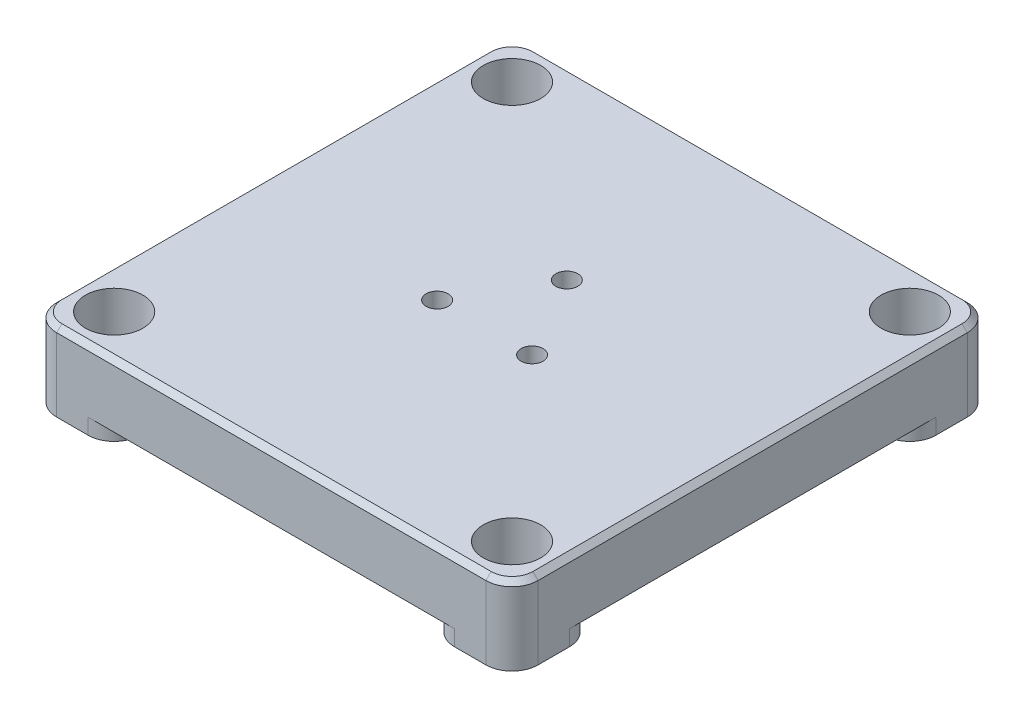
SolidWorks part; units mm, degrees
ref_plane "Спереди" through (0, 0, 0) normal (0, 0, 1) x (1, 0, 0)
ref_plane "Сверху" through (0, 0, 0) normal (0, 1, 0) x (1, 0, 0)
ref_plane "Справа" through (0, 0, 0) normal (1, 0, 0) x (0, 0, -1)
sketch "Эскиз1" plane through (0, 0, 0) normal (0, 1, 0) x (1, 0, 0)
  line L1 (-46.1, 46.1) -> (46.1, 46.1)
  line L2 (-46.1, 46.1) -> (-46.1, -46.1)
  line L3 (-46.1, -46.1) -> (46.1, -46.1)
  line L4 (46.1, 46.1) -> (46.1, -46.1)
  line L5 (-46.1, 46.1) -> (46.1, -46.1) construction
  line L6 (-46.1, -46.1) -> (46.1, 46.1) construction
  line L7 (38.1, 38.1) -> (-38.1, 38.1) construction
  line L8 (38.1, 38.1) -> (38.1, -38.1) construction
  line L9 (38.1, -38.1) -> (-38.1, -38.1) construction
  line L10 (-38.1, 38.1) -> (-38.1, -38.1) construction
  line L11 (38.1, 38.1) -> (-38.1, -38.1) construction
  line L12 (38.1, -38.1) -> (-38.1, 38.1) construction
  circle A0 centre (0, 0) radius 10.5 construction
  circle A1 centre (0, 10.5) radius 2.1
  circle A2 centre (-38.1, 38.1) radius 3.35
  circle A3 centre (38.1, 38.1) radius 3.35
  circle A4 centre (38.1, -38.1) radius 3.35
  circle A5 centre (-38.1, -38.1) radius 3.35
  circle A6 centre (9.0933, -5.25) radius 2.1
  circle A7 centre (-9.0933, -5.25) radius 2.1
  point P0 (0, 0)
  point P6 (0, 0)
  dimension "D4" = 21
  dimension "D5" = 4.2
  dimension "D6" = 6.7
  dimension "D7" = 6.7
  dimension "D8" = 6.7
  dimension "D9" = 6.7
  dimension "D1" = 92.2
  dimension "D2" = 92.2
  dimension "D3" = 76.2
  dimension "D10" = 3
extrude "Бобышка-Вытянуть1" add sketch "Эскиз1" along normal blind 12
sketch "Эскиз2" plane through (0, 0, 0) normal (0, -1, 0) x (1, 0, 0)
  circle A0 centre (-9.0933, 5.25) radius 3.45
  circle A1 centre (9.0933, 5.25) radius 3.45
  circle A2 centre (0, -10.5) radius 3.45
  dimension "D1" = 6.9
  dimension "D2" = 6.9
  dimension "D3" = 6.9
extrude "Вырез-Вытянуть1" cut sketch "Эскиз2" against normal offset from surface (2 mm away) 10 up to face at (9.0933, 12, 7.35)
sketch "Эскиз3" plane through (0, 0, 0) normal (0, -1, 0) x (1, 0, 0)
  line L0 (30.1, 30.1) -> (46.1, 30.1)
  line L1 (-30.1, 30.1) -> (-46.1, 30.1)
  line L2 (-30.1, 30.1) -> (-30.1, 46.1)
  line L3 (-30.1, 46.1) -> (-46.1, 46.1)
  line L4 (-46.1, 30.1) -> (-46.1, 46.1)
  line L5 (-30.1, 30.1) -> (-46.1, 46.1) construction
  line L6 (-30.1, 46.1) -> (-46.1, 30.1) construction
  line L7 (30.1, 30.1) -> (30.1, 46.1)
  line L8 (30.1, 46.1) -> (46.1, 46.1)
  line L9 (46.1, 30.1) -> (46.1, 46.1)
  line L10 (30.1, -30.1) -> (30.1, -46.1)
  line L11 (30.1, -30.1) -> (46.1, -30.1)
  line L12 (46.1, -30.1) -> (46.1, -46.1)
  line L13 (30.1, -46.1) -> (46.1, -46.1)
  line L14 (-30.1, -30.1) -> (-46.1, -30.1)
  line L15 (-30.1, -30.1) -> (-30.1, -46.1)
  line L16 (-30.1, -46.1) -> (-46.1, -46.1)
  line L17 (-46.1, -30.1) -> (-46.1, -46.1)
  line L18 (46.1, 46.1) -> (46.1, -46.1) construction
  line L19 (-46.1, 46.1) -> (46.1, 46.1) construction
  circle A0 centre (-38.1, 38.1) radius 3.35
  circle A1 centre (38.1, 38.1) radius 3.35
  circle A2 centre (38.1, -38.1) radius 3.35
  circle A3 centre (-38.1, -38.1) radius 3.35
  circle A4 centre (38.1, 38.1) radius 3.35 construction
  point P0 (-38.1, 38.1)
  dimension "D1" = 4
  dimension "D2" = 4
extrude "Бобышка-Вытянуть2" add sketch "Эскиз3" along normal blind 3
sketch "Эскиз4" plane through (0, 12, 0) normal (0, 1, 0) x (1, 0, 0)
  circle A0 centre (38.1, 38.1) radius 5.5
  circle A1 centre (38.1, -38.1) radius 5.5
  circle A2 centre (-38.1, -38.1) radius 5.5
  circle A3 centre (-38.1, 38.1) radius 5.5
  circle A4 centre (-38.1, 38.1) radius 3.35 construction
  dimension "D1" = 11
  dimension "D2" = 4
extrude "Вырез-Вытянуть2" cut sketch "Эскиз4" against normal offset from surface (10.8 mm away) 4.2 up to face at (38.1, -3, -38.1)
fillet "Скругление1" radius 5 16 edges at (-30.1, -1.5, 46.1) (-46.1, -1.5, 30.1) (-46.1, -1.5, -30.1) (-30.1, -1.5, -46.1) (30.1, -1.5, -46.1) (46.1, -1.5, -30.1) (46.1, -1.5, 30.1) (30.1, -1.5, 46.1) (-30.1, -1.5, 30.1) (30.1, -1.5, 30.1) (30.1, -1.5, -30.1) (-30.1, -1.5, -30.1) (-46.1, 4.5, -46.1) (46.1, 4.5, -46.1) (-46.1, 4.5, 46.1) (46.1, 4.5, 46.1)
chamfer "Фаска1" distance 1 angle 45 8 edges at (0, 12, -46.1) (-44.6355, 12, -44.6355) (44.6355, 12, -44.6355) (-46.1, 12, 0) (46.1, 12, 0) (-44.6355, 12, 44.6355) (44.6355, 12, 44.6355) (0, 12, 46.1)
equation "\"motor_diameter\"= 30"
equation "\"mm_diameter\"= IIF ( \"motor_diameter\" < 34 , 41 , \"motor_diameter\" + 8 )"
equation "\"upper_shafts_diameter\"= 5"
equation "\"upper_shats_length\"= 180"
equation "\"upper_bearing_d1\"= 10"
equation "\"upper_bearing_d2\"= 5"
equation "\"upper_bearing_h\"= 15"
equation "\"lower_shafts_diameter\"= 5"
equation "\"lower_shafts_length\"= 180"
equation "\"lower_bearing_d1\"= 10"
equation "\"lower_bearing_d2\"= 5"
equation "\"lower_bearing_h\"= 15"
equation "\"print_offset\"= 0.2"
equation "\"bh_screws_d\"= 2"
equation "\"bh_screws_h\"= 20"
equation "\"bh_screws_hh_d\"= 3.4"
equation "\"bh_screws_hh_h\"= 2"
equation "\"bh_nut_d\"= 3.8"
equation "\"bh_nut_h\"= 2"
equation "\"motor_screws_d\"= 3"
equation "\"motor_screws_h\"= 16"
equation "\"motor_screws_hh_d\"= 5.5"
equation "\"motor_screws_hh_h\"= 3"
equation "\"plate_hole_distance\"= 25.4"
equation "\"plate_screws_d\"= 6.5"
equation "\"shafts_diameter\"= IIF ( \"mm_diameter\" < 42 , 42 + 8 , \"mm_diameter\" + 8 )"
equation "\"central_hole_diameter\"= 8"
equation "\"bh_thikness\"= 4"
equation "\"ends_screws_d\"= 4"
equation "\"ends_screws_h\"= 16"
equation "\"ends_screws_hh_d\"= 6.7"
equation "\"ends_screws_hh_h\"= 4.1"
equation "\"ends_nut_d\"= 6.8"
equation "\"ends_nut_h\"= 3"
equation "\"D1@Эскиз1\"=\"D3@Эскиз1\"+16"
equation "\"D2@Эскиз1\"=\"D1@Эскиз1\""
equation "\"D3@Эскиз1\"=\"plate_hole_distance\"*3"
equation "\"D5@Эскиз1\"=\"ends_screws_d\"+\"print_offset\""
equation "\"D6@Эскиз1\"=\"plate_screws_d\"+\"print_offset\""
equation "\"D7@Эскиз1\"=\"D6@Эскиз1\""
equation "\"D8@Эскиз1\"=\"D6@Эскиз1\""
equation "\"D9@Эскиз1\"=\"D6@Эскиз1\""
equation "\"D1@Эскиз2\"=\"ends_screws_hh_d\"+\"print_offset\""
equation "\"D2@Эскиз2\"=\"D1@Эскиз2\""
equation "\"D3@Эскиз2\"=\"D1@Эскиз2\""
equation "\"D1@Вырез-Вытянуть1\"=\"ends_screws_h\"-6"
equation "\"system_radius\" = ( \"shafts_diameter\" + 12 + \"bh_thikness\" / 2 ) / 2"
equation "\"encoder_distance\"= \"system_radius\" + 4"
equation "\"tape_position\"= \"encoder_distance\" - 2 + 3.9 + 1.7 / 2"
equation "\"ft_sensor_d1\" = 9.8"
equation "\"ft_sensor_d2\"= 24.9"
equation "\"ft_sensor_h\"= 7"
equation "\"carbon_pipe_d\"= 14"
